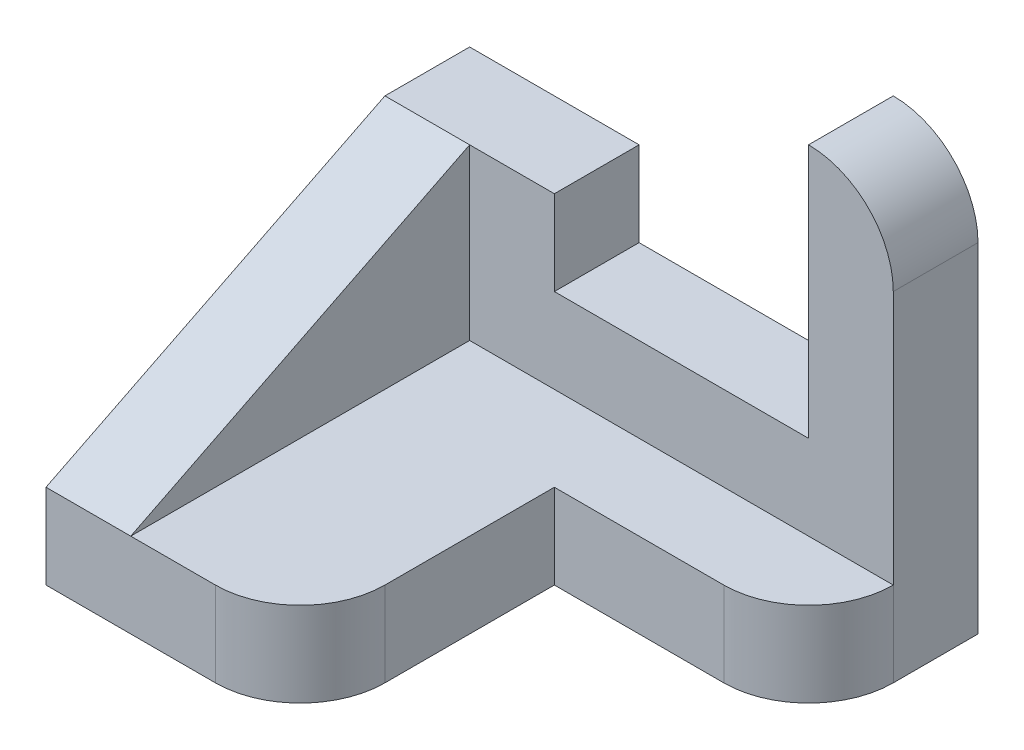
SolidWorks part; units mm, degrees
ref_plane "Front Plane" through (0, 0, 0) normal (0, 0, 1) x (1, 0, 0)
ref_plane "Top Plane" through (0, 0, 0) normal (0, 1, 0) x (1, 0, 0)
ref_plane "Right Plane" through (0, 0, 0) normal (1, 0, 0) x (0, 0, -1)
sketch "Sketch1" plane through (0, 0, 0) normal (0, 1, 0) x (1, 0, 0)
  line L0 (0, 0) -> (0, 50)
  line L1 (0, 50) -> (60, 50)
  line L2 (60, 50) -> (60, 40)
  line L3 (50, 30) -> (30, 30)
  line L4 (30, 30) -> (30, 10)
  line L5 (20, 0) -> (0, 0)
  arc A0 (60, 40) -> (50, 30) centre (50, 40) cw
  arc A1 (30, 10) -> (20, 0) centre (20, 10) cw
  point P9 (4.0189, 5.3191)
  point P10 (60, 30)
  point P13 (30, 0)
  dimension "D5" = 10
  dimension "D1" = 50
  dimension "D2" = 60
  dimension "D3" = 30
  dimension "D4" = 20
extrude "Boss-Extrude1" add sketch "Sketch1" along normal blind 10
ref_plane "Plane1" through (0, 0, -50) normal (0, 0, 1) x (1, 0, 0)
sketch "Sketch3" plane through (0, 0, -50) normal (0, 0, 1) x (1, 0, 0)
  line L0 (60, 10) -> (60, 50)
  line L1 (60, 50) -> (50, 50)
  line L2 (50, 50) -> (50, 20)
  line L3 (50, 20) -> (20, 20)
  line L4 (20, 20) -> (20, 30)
  line L5 (20, 30) -> (0, 30)
  line L6 (0, 30) -> (0, 0)
  line L7 (0, 0) -> (60, 0)
  line L8 (60, 0) -> (60, 10)
  dimension "D1" = 30
  dimension "D2" = 40
  dimension "D3" = 30
  dimension "D4" = 30
  dimension "D5" = 20
extrude "Boss-Extrude3" add sketch "Sketch3" along normal blind 10
fillet "Fillet1" radius 10 1 edges at (60, 50, -45)
ref_plane "Plane2" through (0, 0, 0) normal (-1, 0, 0) x (0, 0, 1)
sketch "Sketch5" plane through (0, 0, 0) normal (-1, 0, 0) x (0, 0, 1)
  line L0 (-40, 30) -> (0, 10)
rib "Rib1" sketch "Sketch5" sketch "Sketch5" thickness 10 extrusion direction parallel to sketch draft on no parameters "D1"=10
